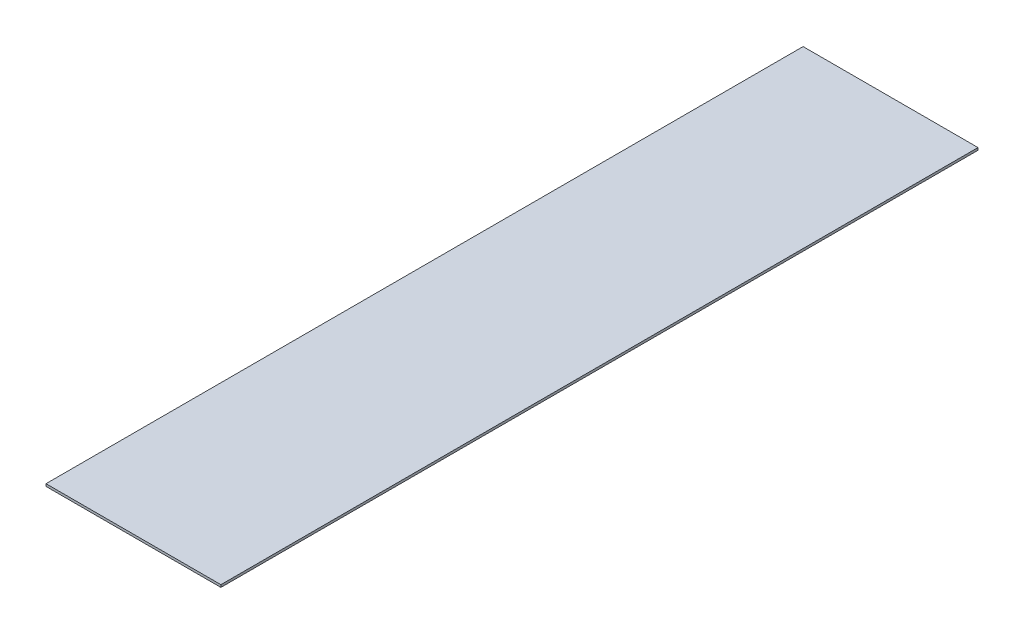
SolidWorks part; units mm, degrees
ref_plane "Front Plane" through (0, 0, 0) normal (0, 0, 1) x (1, 0, 0)
ref_plane "Top Plane" through (0, 0, 0) normal (0, 1, 0) x (1, 0, 0)
ref_plane "Right Plane" through (0, 0, 0) normal (1, 0, 0) x (0, 0, -1)
sketch "Sketch1" plane through (0, 0, 0) normal (0, 1, 0) x (1, 0, 0)
  line L1 (-90.4488, 82.5345) -> (94.9712, 82.5345)
  line L2 (-90.4488, 82.5345) -> (-90.4488, -720.1055)
  line L3 (-90.4488, -720.1055) -> (94.9712, -720.1055)
  line L4 (94.9712, 82.5345) -> (94.9712, -720.1055)
  dimension "D1" = 185.42
  dimension "D2" = 802.64
extrude "Boss-Extrude1" add sketch "Sketch1" along normal blind 2.54
